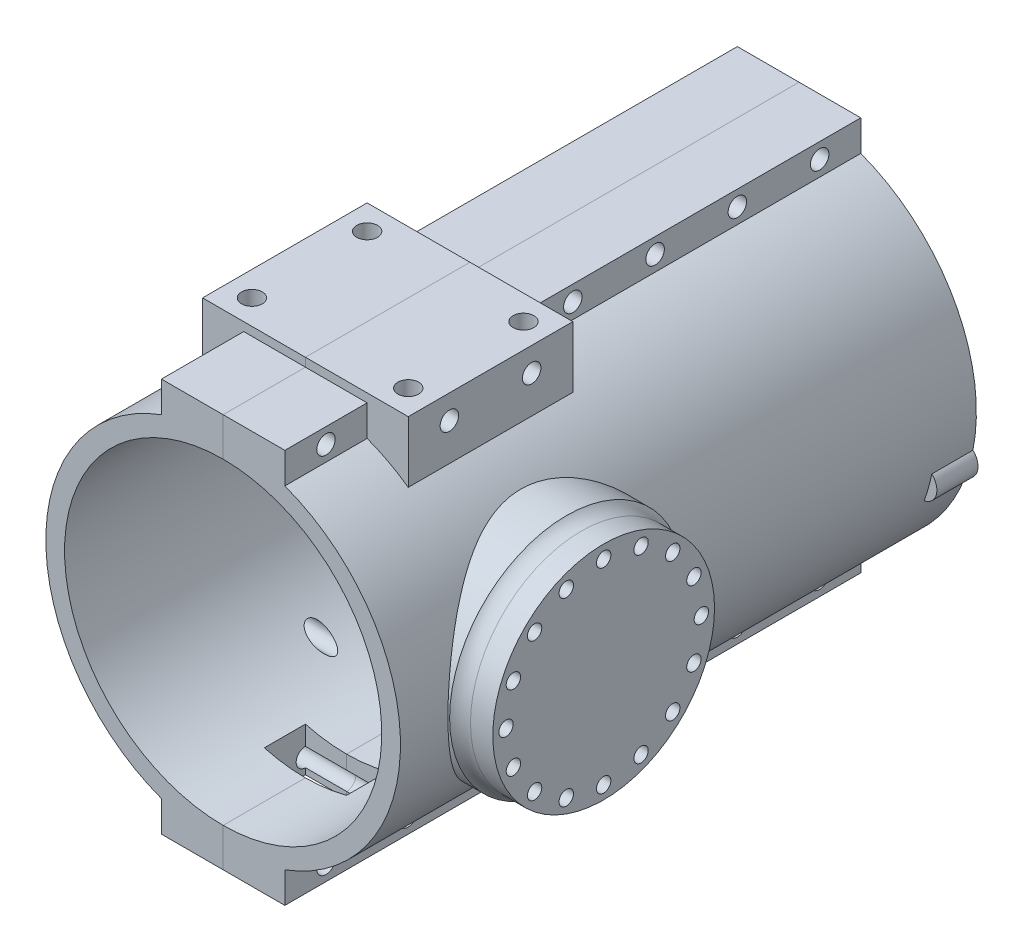
SolidWorks part; units mm, degrees
other "Markup1"
sketch "Sketch14" plane through (-43.1, 43.1, 140) normal (-0.1765, 0.0048, 0.9843) x (0.9842, -0.0149, 0.1765)
other "Markup2"
sketch "Sketch23" plane through (45.1, -43.1, 140) normal (0.9491, -0.0629, 0.3087) x (0.311, 0.031, -0.9499)
ref_plane "Front Plane" through (0, 0, 0) normal (0, 0, 1) x (1, 0, 0)
ref_plane "Top Plane" through (0, 0, 0) normal (0, 1, 0) x (1, 0, 0)
ref_plane "Right Plane" through (0, 0, 0) normal (1, 0, 0) x (0, 0, -1)
sketch "Sketch1" plane through (0, 0, 0) normal (0, 0, 1) x (1, 0, 0)
  circle A1 centre (0, 0) radius 43.1
  dimension "D1" = 86.2
extrude "Main Body" add sketch "Sketch1" along normal blind 140
ref_plane "Plane1" through (0, 43.1, 0) normal (0, 1, 0) x (1, 0, 0)
sketch "Sketch34" [suppressed] plane through (0, 43.1, 0) normal (0, 1, 0) x (1, 0, 0)
  line L6 (-5, -13) -> (5, -13)
  line L8 (-5, -13) -> (-5, -3)
  line L9 (-5, -3) -> (5, -3)
  line L10 (5, -13) -> (5, -3)
  line L11 (-5, -13) -> (5, -3) construction
  line L12 (-5, -3) -> (5, -13) construction
  point P0 (0, -8)
  dimension "D1" = 8
  dimension "D2" = 10
  dimension "D3" = 10
sketch "Sketch6" plane through (0, 43.1, 0) normal (0, 1, 0) x (1, 0, 0)
  line L2 (-5, -47.7) -> (5, -47.7)
  line L3 (-5, -47.7) -> (-5, -37.7)
  line L4 (-5, -37.7) -> (5, -37.7)
  line L5 (5, -47.7) -> (5, -37.7)
  line L6 (-5, -47.7) -> (5, -37.7) construction
  line L7 (-5, -37.7) -> (5, -47.7) construction
  point P2 (0, -42.7)
  dimension "D2" = 10
  dimension "D1" = 42.7
  dimension "D3" = 10
extrude "Cut-Extrude3" cut sketch "Sketch6" against normal through all
pattern_circular "Rotated Plug Pattern" count 2 every 90 about axis through (0, 0, 140) along (0, 0, 1) of "Cut-Extrude3"
ref_plane "Plane2" through (52.5, 0, 0) normal (1, 0, 0) x (0, 0, -1)
sketch "Sketch8" plane through (52.5, 0, 0) normal (1, 0, 0) x (0, 0, -1)
  circle A0 centre (-100, 0) radius 26.95
  dimension "D1" = 53.9
  dimension "D2" = 100
extrude "Boss-Extrude2" add sketch "Sketch8" against normal blind 20
mirror "Mirror1" [suppressed] about plane through (0, 0, 0) normal (1, 0, 0)
ref_plane "Plane3" through (0, 50, 0) normal (0, 1, 0) x (1, 0, 0)
sketch "Sketch33" plane through (0, 50, 0) normal (0, 1, 0) x (1, 0, 0)
  line L1 (-25, -120) -> (25, -120)
  line L2 (-25, -120) -> (-25, -80)
  line L3 (-25, -80) -> (25, -80)
  line L4 (25, -120) -> (25, -80)
  line L5 (-25, -120) -> (25, -80) construction
  line L6 (-25, -80) -> (25, -120) construction
  point P0 (0, -100)
  dimension "D1" = 100
  dimension "D2" = 40
  dimension "D3" = 50
extrude "Boss-Extrude11" add sketch "Sketch33" against normal blind 22
sketch "Sketch35" plane through (0, 50, 0) normal (0, 1, 0) x (1, 0, 0)
  line L0 (-25, -120) -> (-25, -80) construction
  line L1 (25, -120) -> (25, -80) construction
  line L2 (25, -80) -> (-25, -80) construction
  line L3 (-25, -120) -> (25, -120) construction
  circle A0 centre (-19, -86) radius 2.525
  circle A1 centre (19, -86) radius 2.525
  circle A2 centre (-19, -114) radius 2.525
  circle A3 centre (19, -114) radius 2.525
  dimension "D1" = 5.05
  dimension "D2" = 6
  dimension "D3" = 6
  dimension "D4" = 6
  dimension "D5" = 6
extrude "Cut-Extrude14" cut sketch "Sketch35" against normal blind 4
sketch "Sketch5" plane through (0, 0, 140) normal (0, 0, 1) x (1, 0, 0)
  circle A0 centre (0, 0) radius 32
  dimension "D1" = 64
extrude "Hole 1" cut sketch "Sketch5" against normal through all
sketch "Sketch27" plane through (0, 0, 0) normal (1, 0, 0) x (0, 0, -1)
  line L1 (-100, -36.5) -> (-60, -36.5)
  line L2 (-100, -36.5) -> (-100, -27.5)
  line L3 (-100, -27.5) -> (-60, -27.5)
  line L4 (-60, -36.5) -> (-60, -27.5)
  dimension "D1" = 60
  dimension "D2" = 27.5
  dimension "D3" = 40
  dimension "D4" = 9
extrude "Boss-Extrude9" add sketch "Sketch27" along normal blind 33 and the other way blind 33
sketch "Sketch11" plane through (0, 0, 0) normal (1, 0, 0) x (0, 0, -1)
  circle A0 centre (-65, -32) radius 2.25
  circle A1 centre (-95, -32) radius 2.25
  dimension "D3" = 4.5
  dimension "D1" = 65
  dimension "D2" = 32
  dimension "D4" = 30
extrude "Cut-Extrude6" cut sketch "Sketch11" against normal through all both and the other way through all
sketch "Sketch28" plane through (-33, 0, 0) normal (-1, 0, 0) x (0, 0, 1)
  line L0 (62.8927, -28.35) -> (67.1073, -28.35)
  line L1 (67.1073, -28.35) -> (69.2147, -32)
  line L2 (69.2147, -32) -> (67.1073, -35.65)
  line L3 (67.1073, -35.65) -> (62.8927, -35.65)
  line L4 (62.8927, -35.65) -> (60.7853, -32)
  line L6 (60.7853, -32) -> (62.8927, -28.35)
  line L7 (92.8927, -28.35) -> (97.1073, -28.35)
  line L8 (97.1073, -28.35) -> (99.2147, -32)
  line L9 (99.2147, -32) -> (97.1073, -35.65)
  line L10 (97.1073, -35.65) -> (92.8927, -35.65)
  line L11 (92.8927, -35.65) -> (90.7853, -32)
  line L12 (90.7853, -32) -> (92.8927, -28.35)
  circle A0 centre (65, -32) radius 3.65 construction
  circle A1 centre (65, -32) radius 2.25 construction
  circle A2 centre (95, -32) radius 3.65 construction
  circle A3 centre (95, -32) radius 2.25 construction
  dimension "D2" = 7.3
extrude "Cut-Extrude7" cut sketch "Sketch28" against normal blind 3
sketch "Sketch29" plane through (33, 0, 0) normal (1, 0, 0) x (0, 0, -1)
  circle A0 centre (-95, -32) radius 3.6
  circle A1 centre (-65, -32) radius 3.6
  dimension "D1" = 7.2
extrude "Cut-Extrude8" cut sketch "Sketch29" against normal blind 4
sketch "Sketch2" plane through (0, 0, 140) normal (0, 0, 1) x (1, 0, 0)
  circle A0 centre (0, 0) radius 38.55
  dimension "D1" = 77.1
extrude "Cut-Extrude5" cut sketch "Sketch2" against normal blind 135
sketch "Sketch9" plane through (0, 0, 5) normal (0, 0, 1) x (1, 0, 0)
  circle A0 centre (0, 0) radius 38.55
  circle A1 centre (0, 0) radius 36.89
  circle A2 centre (0, 0) radius 38.55 construction
  dimension "D2" = 1.66
extrude "Boss-Extrude3" add sketch "Sketch9" along normal blind 10
extrude "Cut-Extrude13" [suppressed] cut sketch "Sketch34" against normal blind 15
sketch "Sketch30" plane through (52.5, 0, 0) normal (1, 0, 0) x (0, 0, -1)
  line L0 (-100, 23.75) -> (-100, 0) construction
  circle A0 centre (-100, 0) radius 23.75 construction
  circle A1 centre (-100, 23.75) radius 1.75
  circle A2 centre (-90.9113, 21.9421) radius 1.75
  circle A3 centre (-83.2062, 16.7938) radius 1.75
  circle A4 centre (-78.0579, 9.0887) radius 1.75
  circle A5 centre (-76.25, 0) radius 1.75
  circle A6 centre (-78.0579, -9.0887) radius 1.75
  circle A7 centre (-83.2062, -16.7938) radius 1.75
  circle A8 centre (-90.9113, -21.9421) radius 1.75
  circle A9 centre (-100, -23.75) radius 1.75
  circle A10 centre (-109.0887, -21.9421) radius 1.75
  circle A11 centre (-116.7938, -16.7938) radius 1.75
  circle A12 centre (-121.9421, -9.0887) radius 1.75
  circle A13 centre (-123.75, 0) radius 1.75
  circle A14 centre (-121.9421, 9.0887) radius 1.75
  circle A15 centre (-116.7938, 16.7938) radius 1.75
  circle A16 centre (-109.0887, 21.9421) radius 1.75
  point P38 (-100, 0)
  dimension "D1" = 47.5
  dimension "D2" = 3.5
  dimension "D3" = 16
extrude "Cut-Extrude9" cut sketch "Sketch30" against normal up to surface (22.1349 mm away) up to face at (38.55, 0, 15)
sketch "Sketch31" plane through (52.5, 0, 0) normal (1, 0, 0) x (0, 0, -1)
  line L0 (0, -43.1) -> (0, 43.1) construction
  line L1 (0, -15) -> (-10, -15)
  line L2 (0, -15) -> (0, -7.5)
  line L3 (0, -7.5) -> (-10, -7.5)
  line L4 (-10, -15) -> (-10, -7.5)
  dimension "D1" = 15
  dimension "D2" = 7.5
  dimension "D3" = 10
extrude "Boss-Extrude10" add sketch "Sketch31" against normal up to body from offset 9 offset against normal yes
sketch "Sketch32" plane through (0, 0, 0) normal (0, 0, -1) x (-1, 0, 0)
  line L0 (-43.5, -11.25) -> (-29.9573, -11.25) construction
  line L1 (-43.5, -15) -> (-43.5, -7.5) construction
  line L3 (-42.4424, -7.5) -> (-43.5, -7.5) construction
  line L5 (-43.5, -15) -> (-43.5, -7.5)
  line L6 (-43.5, -7.5) -> (-42.4424, -7.5)
  circle A0 centre (0, 0) radius 32 construction
  arc A2 (-40.4056, -15) -> (-42.4424, -7.5) centre (0, 0) ccw construction
  arc A3 (-40.4056, -15) -> (-42.2658, -8.4385) centre (-39.6806, -11.25) cw
  arc A4 (-42.2658, -8.4385) -> (-42.4424, -7.5) centre (0, 0) cw
  line M3 (-42.4424, -7.5) -> (-43.5, -7.5)
  line M4 (-43.5, -7.5) -> (-43.5, -15)
  line M5 (-43.5, -15) -> (-40.4056, -15)
extrude "Cut-Extrude10" cut sketch "Sketch32" against normal up to surface (10 mm away) contours M4 M3 | L5 M5 region at (43.0347, -8.5479, 0) region at (42.7123, -14.1508, 0) up to face at (42.5043, -11.2615, 10)
ref_plane "Plane4" through (-43.1, 0, 0) normal (-1, 0, 0) x (0, 0, 1)
sketch "Sketch36" plane through (-43.1, 0, 0) normal (-1, 0, 0) x (0, 0, 1)
  line L0 (140, -43.1) -> (140, 43.1) construction
  line L1 (52.58, 43.1) -> (-52.58, 43.1) construction
  circle A0 centre (110, 8.1) radius 19.05
  dimension "D1" = 38.1
  dimension "D2" = 30
  dimension "D3" = 35
extrude "Cut-Extrude15" [suppressed] cut sketch "Sketch36" against normal up to next
sketch "Sketch37" plane through (52.5, 0, 0) normal (1, 0, 0) x (0, 0, -1)
  circle A0 centre (-100, 23.75) radius 1.75 construction
  circle A1 centre (-90.9113, 21.9421) radius 1.75 construction
  circle A2 centre (-83.2062, 16.7938) radius 1.75 construction
  circle A3 centre (-78.0579, 9.0887) radius 1.75 construction
  circle A4 centre (-76.25, 0) radius 1.75 construction
  circle A5 centre (-78.0579, -9.0887) radius 1.75 construction
  circle A6 centre (-83.2062, -16.7938) radius 1.75 construction
  circle A7 centre (-90.9113, -21.9421) radius 1.75 construction
  circle A8 centre (-100, -23.75) radius 1.75 construction
  circle A9 centre (-109.0887, -21.9421) radius 1.75 construction
  circle A10 centre (-116.7938, -16.7938) radius 1.75 construction
  circle A11 centre (-121.9421, -9.0887) radius 1.75 construction
  circle A12 centre (-123.75, 0) radius 1.75 construction
  circle A13 centre (-121.9421, 9.0887) radius 1.75 construction
  circle A14 centre (-116.7938, 16.7938) radius 1.75 construction
  circle A15 centre (-109.0887, 21.9421) radius 1.75 construction
  circle A16 centre (-100, 23.75) radius 1.75
  circle A17 centre (-90.9113, 21.9421) radius 1.75
  circle A18 centre (-83.2062, 16.7938) radius 1.75
  circle A19 centre (-78.0579, 9.0887) radius 1.75
  circle A20 centre (-76.25, 0) radius 1.75
  circle A21 centre (-78.0579, -9.0887) radius 1.75
  circle A22 centre (-83.2062, -16.7938) radius 1.75
  circle A23 centre (-90.9113, -21.9421) radius 1.75
  circle A24 centre (-100, -23.75) radius 1.75
  circle A25 centre (-109.0887, -21.9421) radius 1.75
  circle A26 centre (-116.7938, -16.7938) radius 1.75
  circle A27 centre (-121.9421, -9.0887) radius 1.75
  circle A28 centre (-123.75, 0) radius 1.75
  circle A29 centre (-121.9421, 9.0887) radius 1.75
  circle A30 centre (-116.7938, 16.7938) radius 1.75
  circle A31 centre (-109.0887, 21.9421) radius 1.75
  circle A32 centre (-100, 23.75) radius 3.75
  circle A33 centre (-90.9113, 21.9421) radius 3.75
  circle A34 centre (-83.2062, 16.7938) radius 3.75
  circle A35 centre (-78.0579, 9.0887) radius 3.75
  circle A36 centre (-76.25, 0) radius 3.75
  circle A37 centre (-78.0579, -9.0887) radius 3.75
  circle A38 centre (-83.2062, -16.7938) radius 3.75
  circle A39 centre (-90.9113, -21.9421) radius 3.75
  circle A40 centre (-100, -23.75) radius 3.75
  circle A41 centre (-109.0887, -21.9421) radius 3.75
  circle A42 centre (-116.7938, -16.7938) radius 3.75
  circle A43 centre (-121.9421, -9.0887) radius 3.75
  circle A44 centre (-123.75, 0) radius 3.75
  circle A45 centre (-121.9421, 9.0887) radius 3.75
  circle A46 centre (-116.7938, 16.7938) radius 3.75
  circle A47 centre (-109.0887, 21.9421) radius 3.75
  circle M1 centre (-109.0887, 21.9421) radius 1.75
  circle M2 centre (-116.7938, 16.7938) radius 1.75
  circle M3 centre (-121.9421, 9.0887) radius 1.75
  circle M4 centre (-123.75, 0) radius 1.75
  circle M5 centre (-121.9421, -9.0887) radius 1.75
  circle M6 centre (-116.7938, -16.7938) radius 1.75
  circle M7 centre (-109.0887, -21.9421) radius 1.75
  circle M8 centre (-100, -23.75) radius 1.75
  circle M9 centre (-90.9113, -21.9421) radius 1.75
  circle M10 centre (-83.2062, -16.7938) radius 1.75
  circle M11 centre (-78.0579, -9.0887) radius 1.75
  circle M12 centre (-76.25, 0) radius 1.75
  circle M13 centre (-78.0579, 9.0887) radius 1.75
  circle M14 centre (-83.2062, 16.7938) radius 1.75
  circle M15 centre (-90.9113, 21.9421) radius 1.75
  circle M16 centre (-100, 23.75) radius 1.75
  circle M17 centre (-100, 0) radius 26.95
  dimension "D1" = 2
extrude "Boss-Extrude13" add sketch "Sketch37" against normal blind 5 from offset 18 contours A47 M17 M1 | A47 M17 | A32 M17 M16 | A32 M17 | A33 M17 M15 | A33 M17 | A40 M17 M8 | A40 M17 | A39 M17 M9 | A39 M17 | A41 M17 | A41 M17 M7 region at (52.5, 20.5336, 101.7207) region at (52.5, 27.1554, 100) region at (52.5, 24.801, 89.7271) region at (52.5, 25.0884, 89.6081) region at (52.5, 25.0884, 110.3919) region at (52.5, 24.2552, 106.2724) region at (52.5, -24.801, 89.7271) region at (52.5, -25.0884, 89.6081) region at (52.5, -25.0884, 110.3919) region at (52.5, -18.455, 110.1479) region at (52.5, -26.8477, 100) region at (52.5, -27.1554, 100) offset against normal yes
extrude "Cut-Extrude17" cut sketch "Sketch37<6>" along normal blind 9 from offset 30 contours A47 M17 M1 | M1 | A47 M17 | A32 | A33 | A41 | A40 | A39 region at (52.5, 21.9421, 109.0887) region at (52.5, 25.0884, 110.3919) region at (52.5, 24.2552, 106.2724) offset against normal yes
sketch "Sketch37<6>" plane through (52.5, 0, 0) normal (1, 0, 0) x (0, 0, -1) same geometry as "Sketch37"
extrude "Boss-Extrude14" add sketch "Sketch37<7>" against normal blind 10 from offset 10 contours A42 M17 M6 | A42 M17 | A38 M17 M10 | A38 M17 | A46 M17 M2 | A46 M17 | A34 M17 M14 | A34 M17 region at (52.5, 18.9815, 81.0185) region at (52.5, 19.2018, 80.7982) region at (52.5, 19.2018, 119.2018) region at (52.5, 19.6114, 114.4831) region at (52.5, -18.9815, 81.0185) region at (52.5, -19.2018, 80.7982) region at (52.5, -19.2018, 119.2018) region at (52.5, -13.1675, 117.1523) offset against normal yes
sketch "Sketch37<7>" plane through (52.5, 0, 0) normal (1, 0, 0) x (0, 0, -1) same geometry as "Sketch37"
extrude "Cut-Extrude18" cut sketch "Sketch37<8>" along normal blind 13 from offset 30 contours A42 | A38 | A34 | A46 offset against normal yes
sketch "Sketch37<8>" plane through (52.5, 0, 0) normal (1, 0, 0) x (0, 0, -1) same geometry as "Sketch37"
extrude "Boss-Extrude16" add sketch "Sketch37<10>" against normal blind 6 from offset 10 contours A44 M17 M4 | A44 M17 | A43 M17 M5 | A43 M17 | A45 M17 M3 | A45 M17 | A36 M17 M12 | A36 M17 | A35 M17 M13 | A35 M17 | A37 M17 M11 | A37 M17 region at (52.5, 10.2729, 75.199) region at (52.5, 10.3919, 74.9116) region at (52.5, 10.3919, 125.0884) region at (52.5, 12.3035, 120.2253) region at (52.5, 1.0374, 73.1723) region at (52.5, 0, 72.8446) region at (52.5, 0, 127.1554) region at (52.5, 3.4911, 122.6924) region at (52.5, -10.2729, 75.199) region at (52.5, -10.3919, 74.9116) region at (52.5, -10.3919, 125.0884) region at (52.5, -5.4617, 121.5862) offset against normal yes
sketch "Sketch37<10>" plane through (52.5, 0, 0) normal (1, 0, 0) x (0, 0, -1) same geometry as "Sketch37"
extrude "Cut-Extrude19" cut sketch "Sketch37<9>" along normal blind 5.5 from offset 20 contours A44 M17 M4 | A36 M17 M12 | M12 | M4 | A44 M17 | A36 M17 | A43 | A45 | A35 | A37 region at (52.5, 0, 76.25) region at (52.5, 0, 123.75) region at (52.5, 1.0374, 73.1723) region at (52.5, 0, 72.8446) region at (52.5, 0, 127.1554) region at (52.5, 3.4911, 122.6924) offset against normal yes
sketch "Sketch37<9>" plane through (52.5, 0, 0) normal (1, 0, 0) x (0, 0, -1) same geometry as "Sketch37"
sketch "Sketch38" plane through (52.5, 0, 0) normal (1, 0, 0) x (0, 0, -1)
  circle A0 centre (-100, 0) radius 26.95 construction
  circle A1 centre (-100, 0) radius 26.95
  circle A2 centre (-100, 0) radius 28.45
  circle M17 centre (-100, 0) radius 26.95
  dimension "D1" = 1.5
extrude "Boss-Extrude15" add sketch "Sketch38" against normal up to next from offset 9 contours M17 | M17 | M17 | M17 region at (52.5, 0, 127.6453) offset against normal yes
fillet "Fillet1" radius 5 1 edges at (43.5, 0, 73.05)
sketch "Sketch40" plane through (0, 0, 37.7) normal (0, 0, 1) x (1, 0, 0)
  circle A0 centre (0, 0) radius 36.89 construction
  circle A1 centre (0, 0) radius 36.89
  circle A2 centre (0, 0) radius 43.1 construction
  circle A3 centre (0, 0) radius 43.1
extrude "Boss-Extrude17" add sketch "Sketch40" along normal blind 10
extrude "Boss-Extrude18" add sketch "Sketch40<2>" against normal blind 10 from offset 6.35 offset against normal yes
sketch "Sketch40<2>" plane through (0, 0, 37.7) normal (0, 0, 1) x (1, 0, 0) same geometry as "Sketch40"
sketch "Sketch43" plane through (0, 0, 0) normal (0, 0, -1) x (-1, 0, 0)
  line L0 (-15, 40.4056) -> (-15, 47.9056)
  line L1 (-15, 47.9056) -> (15, 47.9056)
  line L2 (15, 47.9056) -> (15, 40.4056)
  arc A0 (-40.4056, -15) -> (-42.2658, -8.4385) centre (0, 0) ccw construction
  arc A1 (15, 40.4056) -> (-15, 40.4056) centre (0, 0) ccw
  dimension "D1" = 7.5
  dimension "D2" = 30
extrude "Boss-Extrude21" add sketch "Sketch43" against normal up to surface (140 mm away) up to face at (38.55, 0, 140)
sketch "Sketch44" plane through (-15, 0, 0) normal (-1, 0, 0) x (0, 0, 1)
  line L0 (0, 40.4056) -> (0, 47.9056) construction
  line L1 (0, 40.4056) -> (0, 47.9056) construction
  line L2 (0, 44.1556) -> (140, 44.1556) construction
  line L3 (140, 40.4056) -> (140, 47.9056) construction
  line L4 (10, 44.1556) -> (30, 44.1556) construction
  circle A0 centre (10, 44.1556) radius 2.25
  circle A1 centre (30, 44.1556) radius 2.25
  circle A2 centre (50, 44.1556) radius 2.25
  circle A3 centre (70, 44.1556) radius 2.25
  circle A4 centre (90, 44.1556) radius 2.25
  circle A5 centre (110, 44.1556) radius 2.25
  circle A6 centre (130, 44.1556) radius 2.25
  dimension "D1" = 4.5
  dimension "D2" = 10
  dimension "D4" = 20
  dimension "D3" = 7
extrude "Cut-Extrude20" cut sketch "Sketch44" against normal up to next
sketch "Sketch45" plane through (-25, 0, 0) normal (-1, 0, 0) x (0, 0, 1)
  circle A0 centre (90, 44.1556) radius 2.25 construction
  circle A1 centre (110, 44.1556) radius 2.25 construction
  circle A2 centre (90, 44.1556) radius 2.25
  circle A3 centre (110, 44.1556) radius 2.25
  circle A4 centre (110, 44.1556) radius 5.25
  circle A5 centre (90, 44.1556) radius 5.25
  dimension "D1" = 3
extrude "Cut-Extrude21" cut sketch "Sketch45" against normal up to next contours A2 | A3 region at (-25, 44.1556, 90) region at (-25, 44.1556, 110)
ref_point "Point1"
ref_plane "Plane5" through (0, 0, 0) normal (0, 1, 0) x (1, 0, 0)
mirror "Mirror2" about plane through (0, 0, 0) normal (0, 1, 0) of "Cut-Extrude20", "Boss-Extrude21"
sketch "Sketch10" plane through (0, 0, 0) normal (0, 1, 0) x (1, 0, 0)
  line L0 (43.1, 0) -> (-43.1, 0) construction
  line L1 (-10, -120) -> (10, -120)
  line L2 (-10, -120) -> (-10, -110)
  line L3 (-10, -110) -> (10, -110)
  line L4 (10, -120) -> (10, -110)
  line L5 (-10, -120) -> (10, -110) construction
  line L6 (-10, -110) -> (10, -120) construction
  point P0 (0, -115)
  point P7 (-10, -115)
  dimension "D1" = 110
  dimension "D2" = 10
  dimension "D3" = 20
extrude "Motor Wire Hole" cut sketch "Sketch10" against normal through all
ref_plane "Plane6" through (0, 0, 0) normal (-1, 0, 0) x (0, 0, 1)
split "Split1" trim tools "Plane6" bodies to split 111 resulting bodies 154 155
